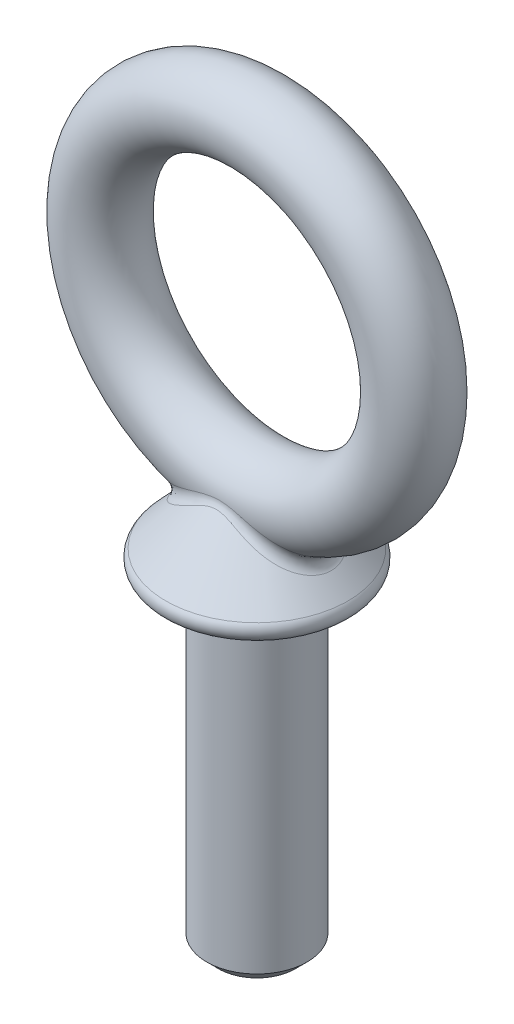
SolidWorks part; units mm, degrees
ref_plane "Front Plane" through (0, 0, 0) normal (0, 0, 1) x (1, 0, 0)
ref_plane "Top Plane" through (0, 0, 0) normal (0, 1, 0) x (1, 0, 0)
ref_plane "Right Plane" through (0, 0, 0) normal (1, 0, 0) x (0, 0, -1)
sketch "Sketch1" plane through (0, 0, 0) normal (0, 0, 1) x (1, 0, 0)
  line L0 (0, -24.6062) -> (0, -70.6438) construction
  line L1 (-6.35, -70.6438) -> (6.35, -70.6438) construction
  line L2 (6.5615, -70.5216) -> (6.5615, -72.4755) construction
  line L3 (0, -24.6062) -> (0, -15.0812) construction
  line L4 (-11.9062, -29.3688) -> (11.9062, -29.3688) construction
  line L5 (6.5615, -72.4755) -> (4.8694, -71.4986) construction
  line L6 (4.8694, -71.4986) -> (6.5615, -70.5216) construction
  line L7 (4.8694, -71.4986) -> (5.0809, -71.4986) construction
  line L8 (6.5615, -71.4986) -> (6.35, -71.4986) construction
  line L9 (5.0809, -71.6207) -> (5.0809, -71.3764) construction
  line L10 (6.35, -72.3534) -> (6.35, -70.6438) construction
  line L11 (6.4558, -72.4144) -> (6.4558, -70.5827) construction
  circle A0 centre (0, 0) radius 24.6062 construction
  circle A1 centre (0, 19.8438) radius 4.7625 construction
  circle A2 centre (0, 0) radius 15.0813 construction
  point P7 (0, -24.6062)
  point P9 (0, -29.3688)
  point P10 (0, 24.6062)
  point P11 (0, 15.0812)
  point P14 (0, -70.6438)
  point P17 (0, 0)
  point P19 (0, -19.8438)
  point P21 (0, -29.3688)
  point P32 (5.0809, -71.4986)
  point P35 (6.35, -71.4986)
  point P38 (6.4558, -71.4986)
  dimension "Pitch" = 1.9538
  dimension "D1" = 0.2442
sketch "Sketch2" plane through (0, 0, 0) normal (0, 1, 0) x (1, 0, 0)
  circle A0 centre (0, 0) radius 6.35
extrude "Boss-Extrude1" add sketch "Sketch2" against normal up to vertex (70.6437 mm away) from vertex up to point (0, -70.6438, 0) starting at point (0, -29.3688, 0)
sketch "Sketch3" plane through (0, -70.6438, 0) normal (0, -1, 0) x (1, 0, 0)
  circle A1 centre (0, 0) radius 6.35
  circle A2 centre (0, 0) radius 6.35
  point P0 (6.35, 0)
  point P1 (0, -6.35)
  dimension "D1" = 0
sketch "Sketch4" plane through (0, 0, 0) normal (0, 0, 1) x (1, 0, 0)
  line L0 (5.0809, -71.3764) -> (5.0809, -71.6207)
  line L1 (5.0809, -71.6207) -> (6.4558, -72.4144)
  line L2 (6.4558, -72.4144) -> (6.4558, -70.5827)
  line L3 (6.4558, -70.5827) -> (5.0809, -71.3764)
sketch "Sketch5" plane through (0, -70.6438, 0) normal (0, -1, 0) x (1, 0, 0)
  circle A0 centre (0, 0) radius 4.8694
extrude "Cut-Extrude1" cut sketch "Sketch5" against normal through all draft 45 flip side to cut
sketch "Sketch6" plane through (0, 0, 0) normal (1, 0, 0) x (0, 0, -1)
  circle A0 centre (0, 19.8438) radius 4.7625
ref_axis "Axis1" through (0, 0, -7.6398) along (0, 0, 1)
revolve "Revolve1" add sketch "Sketch6" angle 360 about axis through (0, 0, -7.6398) along (0, 0, 1)
sketch "Sketch8" plane through (0, 0, 0) normal (0, 0, 1) x (1, 0, 0)
  line L0 (0, -29.3688) -> (0, -19.8438)
  line L1 (0, -19.8438) -> (-4.7625, -19.8438)
  line L2 (-10.5172, -29.3688) -> (-11.9062, -29.3688) construction
  line L3 (-11.9062, -29.3688) -> (-11.9062, -27.9797) construction
  line L4 (0, -29.3688) -> (11.9062, -29.3688) construction
  line L5 (-11.9062, -29.3688) -> (11.9062, -29.3688) construction
  line L6 (-11.5284, -27.0273) -> (-4.7625, -19.8438)
  line L7 (-11.9062, -29.3688) -> (0, -29.3688) construction
  line L9 (-10.5172, -29.3688) -> (0, -29.3688)
  arc A0 (-11.5284, -27.0273) -> (-10.5172, -29.3688) centre (-10.5172, -27.9797) ccw
  circle A1 centre (0, -19.8438) radius 4.7625 construction
  dimension "D1" = 1.3891
revolve "Revolve2" add sketch "Sketch8" angle 360 about L0
fillet "Fillet1" radius 1.3891 1 edges at (7.3014, -22.9015, 2.2575)
sketch "SketchX" plane through (0, 0, 0) normal (1, 0, 0) x (0, 0, -1)
  line L0 (6.35, -70.6438) -> (6.35, -65.7591) construction
  line L1 (0, -70.6438) -> (6.35, -70.6438) construction
  dimension "D1" = 4.8846
  dimension "D2" = 6.35
ref_axis "Center Axis 1" through (0, 21.5506, 0) along (0, -1, 0)
ref_axis "Center Axis 2" through (0, 0, -7.6398) along (0, 0, 1)
equation "\"D1@Sketch1\"=\"Pitch@Sketch1\"/8"
equation "\"Pitch\"= \"Pitch@Sketch1\""
equation "\"D2@SketchX\" = \"Thread OD@Sketch1\" / 2"
